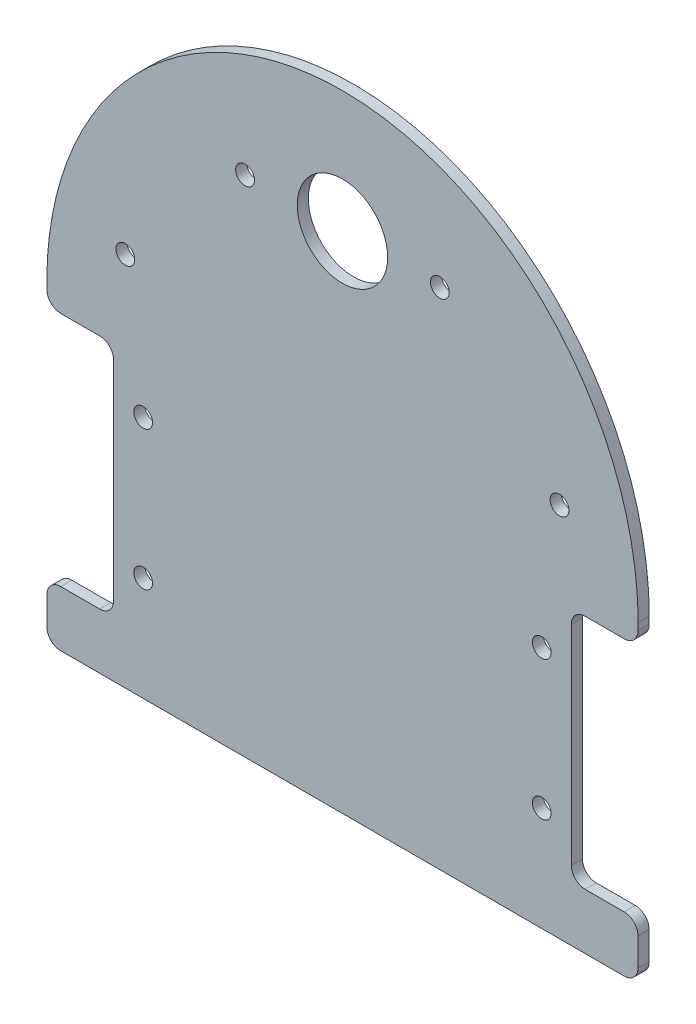
SolidWorks part; units mm, degrees
material "A-Glass Fiber"
ref_plane "Top Plane" through (0, 0, 0) normal (0, 0, 1) x (1, 0, 0)
ref_plane "Right Plane" through (0, 0, 0) normal (0, 1, 0) x (1, 0, 0)
ref_plane "Front Plane" through (0, 0, 0) normal (1, 0, 0) x (0, 0, -1)
sketch "Sketch1" plane through (0, 0, 0) normal (0, 0, 1) x (1, 0, 0)
  line L1 (42.5, -45) -> (-42.5, -45)
  line L2 (42.5, -45) -> (42.5, 45)
  line L3 (42.5, 45) -> (-42.5, 45)
  line L4 (-42.5, -45) -> (-42.5, 45)
  line L5 (42.5, -45) -> (-42.5, 45) construction
  line L6 (42.5, 45) -> (-42.5, -45) construction
  point P0 (0, 0)
  dimension "D1" = 85
  dimension "D2" = 90
extrude "Boss-Extrude1" add sketch "Sketch1" along normal blind 1.6
sketch "Sketch2" plane through (0, 0, 1.6) normal (0, 0, 1) x (1, 0, 0)
  line L0 (-42.5, 45) -> (-42.5, -45) construction
  line L1 (42.5, 45) -> (-42.5, 45) construction
  line L6 (-42.5, 0) -> (-70, 0)
  line L7 (-70, 0) -> (-70, 70)
  line L8 (42.5, -45) -> (42.5, 45) construction
  line L9 (-70, 70) -> (70, 70)
  line L10 (70, 70) -> (70, 0)
  line L11 (70, 0) -> (42.5, 0)
  ellipse E0 centre (0, 0) end of major axis (0, -45) minor radius 42.5 (42.5, 0) -> (-42.5, 0) ccw
  point P14 (0, 70)
  dimension "D1" = 140
  dimension "D2" = 70
extrude "Cut-Extrude1" cut sketch "Sketch2" against normal through all
sketch "Sketch3" plane through (0, 0, 1.6) normal (0, 0, 1) x (1, 0, 0)
  line L1 (-42.5, -3) -> (-32.9, -3)
  line L2 (-42.5, -3) -> (-42.5, -37)
  line L3 (-42.5, -37) -> (-32.9, -37)
  line L4 (-32.9, -3) -> (-32.9, -37)
  line L6 (0, -0.88) -> (0, 0.88) construction
  line L7 (42.5, -3) -> (32.9, -3)
  line L8 (42.5, -37) -> (32.9, -37)
  line L9 (32.9, -3) -> (32.9, -37)
  line L10 (42.5, -3) -> (42.5, -37)
  line L11 (-42.5, 0) -> (-42.5, -45) construction
  line L13 (-42.5, -45) -> (42.5, -45) construction
  dimension "D1" = 9.6
  dimension "D2" = 34
  dimension "D3" = 8
extrude "Cut-Extrude2" cut sketch "Sketch3" against normal through all
sketch "Sketch4" plane through (0, 0, 1.6) normal (0, 0, 1) x (1, 0, 0)
  line L0 (-42.5, -45) -> (42.5, -45) construction
  circle A0 centre (0, 27.5) radius 6.5
  dimension "D1" = 13
  dimension "D2" = 72.5
extrude "Cut-Extrude3" cut sketch "Sketch4" against normal through all
sketch "Sketch5" plane through (0, 0, 1.6) normal (0, 0, 1) x (1, 0, 0)
  line L1 (-32.9, -37) -> (-32.9, -3) construction
  line L2 (-28.65, -10) -> (-28.65, -30) construction
  line L3 (0, -0.88) -> (0, 0.88) construction
  line L4 (-1016.15, -20) -> (48983.85, -20) construction
  line L5 (0, -1000) -> (0, 49000) construction
  circle A0 centre (-28.65, -10) radius 1.35
  circle A1 centre (-28.65, -30) radius 1.35
  circle A2 centre (28.65, -30) radius 1.35
  circle A3 centre (28.65, -10) radius 1.35
  point P2 (-28.65, -20)
  point P14 (-32.9, -20)
  dimension "D3" = 2.7
  dimension "D2" = 20
  dimension "D1" = 4.25
extrude "Cut-Extrude4" cut sketch "Sketch5" against normal through all
sketch "Sketch6" plane through (0, 0, 1.6) normal (0, 0, 1) x (1, 0, 0)
  line L0 (-14, 27.5) -> (14, 27.5) construction
  circle A1 centre (-14, 27.5) radius 1.35
  circle A2 centre (14, 27.5) radius 1.35
  point P5 (0, 27.5)
  dimension "D2" = 2.7
  dimension "D1" = 28
extrude "Cut-Extrude5" cut sketch "Sketch6" against normal through all
sketch "Sketch7" plane through (0, 0, 1.6) normal (0, 0, 1) x (1, 0, 0)
  line L0 (-42.5, -45) -> (42.5, -45) construction
  line L1 (0, -63.3642) -> (0, 76.6358) construction
  line L2 (-31.2085, 9) -> (31.2085, 9) construction
  circle A0 centre (-31.2085, 9) radius 1.35
  circle A1 centre (31.2085, 9) radius 1.35
  point P4 (0, 9)
  dimension "D1" = 2.7
  dimension "D2" = 54
  dimension "D3" = 62.417
extrude "Cut-Extrude6" cut sketch "Sketch7" against normal blind 10
fillet "Fillet1" radius 2 10 edges at (42.5, -37, 0.8) (32.9, -37, 0.8) (32.9, -3, 0.8) (42.5, -3, 0.8) (-32.9, -37, 0.8) (-32.9, -3, 0.8) (-42.5, -37, 0.8) (-42.5, -3, 0.8) (42.5, -45, 0.8) (-42.5, -45, 0.8)
equation "\"Motor_Position\"= 8"
equation "\"D3@Sketch3\"=\"Motor_Position\""
equation "\"Caster_Position\"= 72.5"
equation "\"D2@Sketch4\"=\"Caster_Position\""
equation "\"Battery_Position\"= 54mm"
equation "\"D2@Sketch7\"=\"Battery_Position\""
equation "\"Screw_Hole_Diameter\"= 2.7mm"
equation "\"D3@Sketch5\"=\"Screw_Hole_Diameter\""
equation "\"D2@Sketch6\"=\"Screw_Hole_Diameter\""
equation "\"D1@Sketch7\"=\"Screw_Hole_Diameter\""
